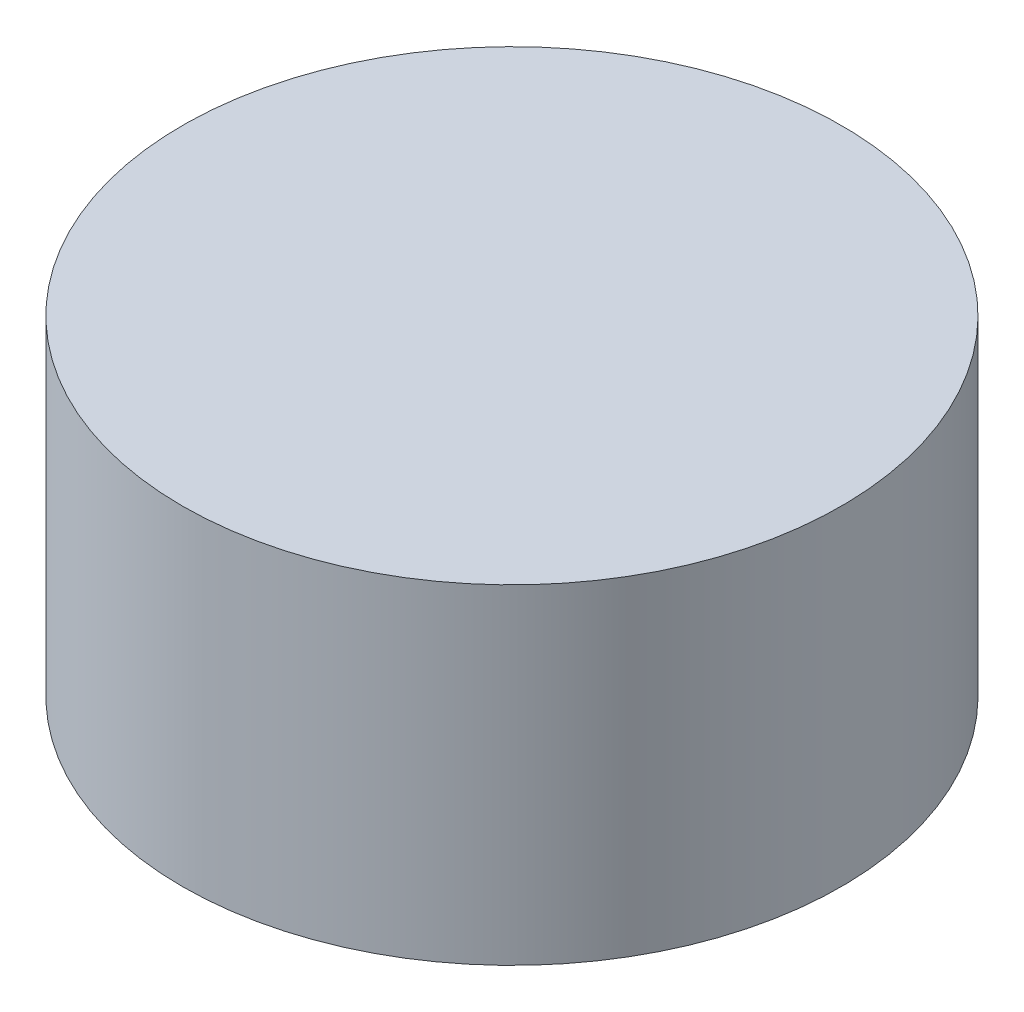
SolidWorks part; units mm, degrees
ref_plane "前视基准面" through (0, 0, 0) normal (0, 0, 1) x (1, 0, 0)
ref_plane "上视基准面" through (0, 0, 0) normal (0, 1, 0) x (1, 0, 0)
ref_plane "右视基准面" through (0, 0, 0) normal (1, 0, 0) x (0, 0, -1)
other "Configuration Table"
sketch "草图1" plane through (0, 0, 0) normal (0, 1, 0) x (1, 0, 0)
  circle A0 centre (0, 0) radius 60
extrude "凸台-拉伸1" add sketch "草图1" along normal blind 60
